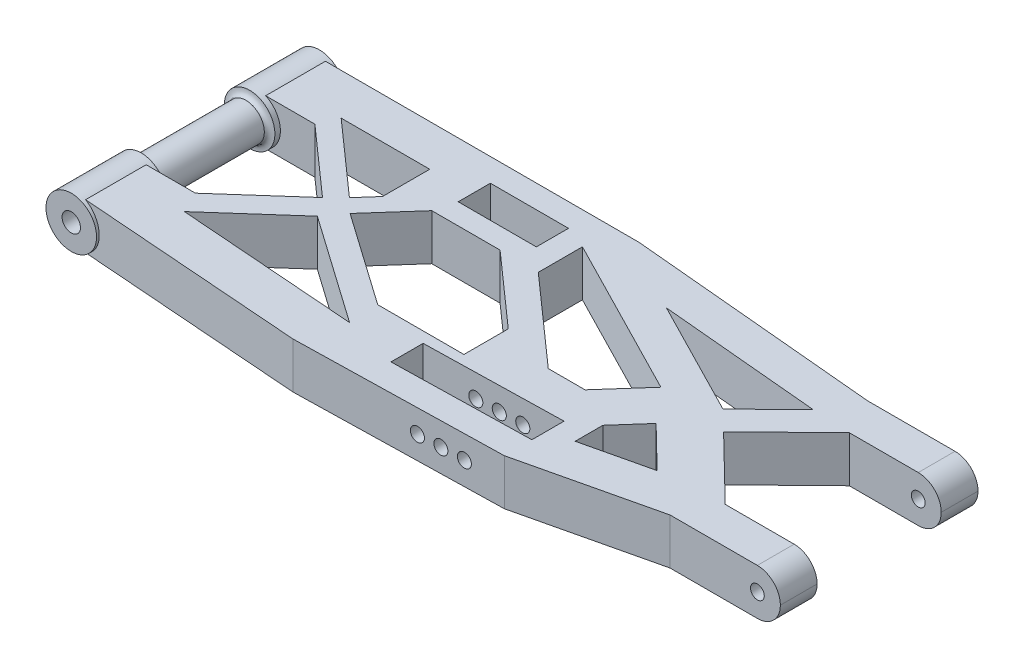
SolidWorks part; units mm, degrees
ref_plane "Plano frontal" through (0, 0, 0) normal (0, 0, 1) x (1, 0, 0)
ref_plane "Plano superior" through (0, 0, 0) normal (0, 1, 0) x (1, 0, 0)
ref_plane "Plano direito" through (0, 0, 0) normal (1, 0, 0) x (0, 0, -1)
sketch "Esboço1" plane through (0, 0, 0) normal (0, 1, 0) x (1, 0, 0)
  line L0 (0, -26) -> (0, 26)
  line L1 (0, 26) -> (70.5, 26)
  line L2 (70.5, 26) -> (125.2723, 21)
  line L3 (125.2723, 21) -> (149.2723, 21)
  line L4 (149.2723, 21) -> (149.2723, -22)
  line L5 (149.2723, -22) -> (125.2723, -22)
  line L6 (125.2723, -22) -> (96.0665, -28.8575)
  line L7 (96.0665, -28.8575) -> (51.0776, -29.8575)
  line L8 (51.0776, -29.8575) -> (0, -26)
  point P14 (0, 0)
  dimension "D1" = 52
  dimension "D2" = 45
  dimension "D3" = 1
  dimension "D4" = 30
  dimension "D5" = 24
  dimension "D6" = 43
  dimension "D7" = 55
  dimension "D8" = 70.5
  dimension "D9" = 24
  dimension "D10" = 5
  dimension "D11" = 51.2231
extrude "Ressalto-extrusão1" add sketch "Esboço1" along normal blind 10
sketch "Esboço2" plane through (0, 0, 0) normal (-1, 0, 0) x (0, 0, 1)
  line L0 (-27, 5) -> (-27, 10.5)
  line L1 (26, 10) -> (26, 0) construction
  line L2 (27, 10.5) -> (11.8, 10.5)
  line L3 (27, 5) -> (27, 10.5)
  line L4 (-26, 10) -> (-26, 0) construction
  line L5 (-27, 10.5) -> (-11.8, 10.5)
  line L6 (-11, 9) -> (11, 9)
  line L7 (-26, 10) -> (26, 10) construction
  line L8 (-27, 5) -> (27, 5)
  spline S0 degree 2 poles (-11.8, 10.5) (-11.7993, 9.25) (-11, 9) knots 0 0 0 1 1 1
  spline S1 degree 2 poles (11.8, 10.5) (11.7824, 9.0255) (11, 9) knots 0 0 0 1 1 1
  point P4 (26, 5)
  point P13 (0, 9)
  point P15 (0, 10)
  dimension "D9" = 1
  dimension "D1" = 15.2
  dimension "D2" = 15.2
  dimension "D3" = 22
  dimension "D4" = 0
  dimension "D5" = 54
  dimension "D6" = 1
  dimension "D7" = 5.5
  dimension "D8" = 0
sketch "Esboço4" plane through (0, 10, 0) normal (0, 1, 0) x (1, 0, 0)
  line L0 (0, -13) -> (13, -13)
  line L1 (0, 27) -> (0, -27) construction
  line L2 (13, -13) -> (13, 13)
  line L3 (13, 13) -> (0, 13)
  line L4 (0, -13) -> (0, 13)
  point P11 (0, 0)
  dimension "D1" = 13
  dimension "D2" = 26
extrude "Corte-extrusão1" cut sketch "Esboço4" against normal through all
revolve "Revolução1" add sketch "Esboço2" angle 360 about L8
sketch "Esboço5" plane through (0, 0, 27) normal (0, 0, 1) x (1, 0, 0)
  circle A0 centre (0, 5) radius 2
  dimension "D1" = 4
extrude "Corte-extrusão2" cut sketch "Esboço5" against normal through all
sketch "Esboço6" plane through (149.2723, 0, 0) normal (1, 0, 0) x (0, 0, -1)
  line L0 (-14, 0) -> (13, 0)
  line L1 (-22, 0) -> (21, 0) construction
  line L2 (13, 0) -> (13, 10)
  line L3 (13, 10) -> (26, 10) construction
  line L4 (13, 10) -> (-14, 10)
  line L5 (-26.173, 10) -> (-13, 10) construction
  line L6 (-14, 10) -> (-14, 0)
  line L8 (21, 10) -> (21, 0) construction
  line L9 (-22, 10) -> (-22, 0) construction
  point P5 (-0.5, 0)
  dimension "D1" = 27
  dimension "D2" = 8
  dimension "D3" = 8
extrude "Corte-extrusão3" cut sketch "Esboço6" against normal blind 20
fillet "Filete1" radius 5 1 edges at (149.2723, 10, 18)
fillet "Filete2" radius 5 3 edges at (149.2723, 0, -17) (149.2723, 10, -17) (149.2723, 0, 18)
sketch "Esboço7" plane through (0, 0, 22) normal (0, 0, 1) x (1, 0, 0)
  circle A0 centre (144.2723, 5) radius 1.5
  dimension "D1" = 3
extrude "Corte-extrusão4" cut sketch "Esboço7" against normal through all
sketch "Esboço8" plane through (0.6886, 0, 30.9776) normal (0.0222, 0, 0.9998) x (0.9998, 0, -0.0222)
  line L0 (95.4015, 10) -> (95.4015, 0) construction
  line L1 (50.4015, 10) -> (95.4015, 10) construction
  circle A0 centre (86.9015, 5) radius 1.5
  circle A1 centre (81.9015, 5) radius 1.5
  circle A2 centre (76.9015, 5) radius 1.5
  dimension "D1" = 3
  dimension "D2" = 8.5
  dimension "D7" = 5
  dimension "D3" = 5
  dimension "D4" = 5
  dimension "D5" = 5
  dimension "D6" = 5
extrude "Corte-extrusão5" cut sketch "Esboço8" against normal blind 20
sketch "Esboço10" plane through (0, 10, 0) normal (0, 1, 0) x (1, 0, 0)
  line L0 (96.0665, -22.8561) -> (66.0739, -23.5227)
  line L1 (66.0739, -23.5227) -> (66.0739, -16.5227)
  line L2 (66.0739, -16.5227) -> (96.0665, -15.8561)
  line L3 (96.0665, -15.8561) -> (96.0665, -22.8561)
  line L4 (13, 13) -> (27.6581, 0)
  line L5 (27.6581, 0) -> (13, -13)
  line L6 (51.0776, -29.8575) -> (96.0665, -28.8575) construction
  line L7 (13, -13) -> (13, 13)
  line L8 (14.7152, 17) -> (30.6055, 2.9072)
  line L9 (30.6055, 2.9072) -> (33.9881, 6.7212)
  line L10 (30.6055, -4.0691) -> (15.2678, -17.6718)
  line L11 (30.6055, -4.0691) -> (54.1571, -20.6089)
  line L13 (15.2678, -17.6718) -> (54.1571, -20.6089)
  line L14 (2.2913, -26.173) -> (51.0776, -29.8575) construction
  line L15 (33.6581, 0) -> (42.0123, 9.4198)
  line L16 (42.0123, 9.4198) -> (56.8717, 9.4198)
  line L17 (56.8717, 9.4198) -> (72.6056, -4.5343)
  line L18 (72.6056, -4.5343) -> (72.6056, -14.1785)
  line L19 (72.6056, -14.1785) -> (53.8474, -14.1785)
  line L20 (43.2155, 13.9661) -> (60.2155, 13.9661)
  line L21 (60.2155, 13.9661) -> (60.2155, 20.9661)
  line L22 (60.2155, 20.9661) -> (43.2155, 20.9661)
  line L23 (43.2155, 20.9661) -> (43.2155, 13.9661)
  line L24 (85.8594, 16.6255) -> (111.0603, 3.7173)
  line L25 (129.2723, -14) -> (115.4199, -0.5)
  line L26 (70.5, 26) -> (2.2913, 26) construction
  line L27 (53.8474, -14.1785) -> (33.6581, 0)
  line L28 (65.2155, 18.9963) -> (65.2155, 9.3875)
  line L29 (33.9881, 6.7212) -> (33.9881, 17)
  line L30 (33.9881, 17) -> (14.7152, 17)
  line L31 (65.2155, 9.3875) -> (84.4425, -7.6646)
  line L32 (115.5114, -15.0471) -> (106.5079, -6.2726)
  line L33 (115.5114, -15.0471) -> (101.0665, -18.4388)
  line L34 (101.0665, -18.4388) -> (101.0665, -12.408)
  line L36 (84.4425, -7.6646) -> (92.452, -7.6646)
  line L37 (92.452, -7.6646) -> (100.2032, 1.0753)
  line L38 (129.2723, -14) -> (129.2723, 13)
  line L39 (96.0665, -28.8575) -> (125.2723, -22) construction
  line L40 (100.2032, 1.0753) -> (65.2155, 18.9963)
  line L41 (115.4199, -0.5) -> (129.2723, 13)
  line L42 (111.0603, 3.7173) -> (121.0127, 13.4164)
  line L43 (121.0127, 13.4164) -> (85.8594, 16.6255)
  line L44 (125.2723, 21) -> (70.5, 26) construction
  line L45 (106.5079, -6.2726) -> (101.0665, -12.408)
  point P53 (60.2155, 17.4661)
  point P73 (122.3461, 6.25)
  dimension "D1" = 30
  dimension "D2" = 7
  dimension "D3" = 6
  dimension "D4" = 0
  dimension "D5" = 9
  dimension "D6" = 5
  dimension "D7" = 4.2128
  dimension "D8" = 0
  dimension "D9" = 5.0843
  dimension "D10" = 19.5923
  dimension "D11" = 28.7792
  dimension "D13" = 24.6706
  dimension "D14" = 5
  dimension "D15" = 18.7582
  dimension "D16" = 5
  dimension "D17" = 6.5139
  dimension "D18" = 39
  dimension "D19" = 5.5122
  dimension "D20" = 14.8594
  dimension "D21" = 19.3427
  dimension "D22" = 13.8969
  dimension "D23" = 7.9394
  dimension "D24" = 28.3145
  dimension "D25" = 7
  dimension "D26" = 17
  dimension "D27" = 7.3011
  dimension "D28" = 5.0339
  dimension "D29" = 9.4543
  dimension "D30" = 19.2729
  dimension "D31" = 9
  dimension "D32" = 4.1307
  dimension "D33" = 4.5463
  dimension "D34" = 39.3103
  dimension "D35" = 9.5924
  dimension "D36" = 8.2007
  dimension "D37" = 12.572
  dimension "D38" = 6.0629
extrude "Corte-extrusão8" cut sketch "Esboço10" against normal blind 10
